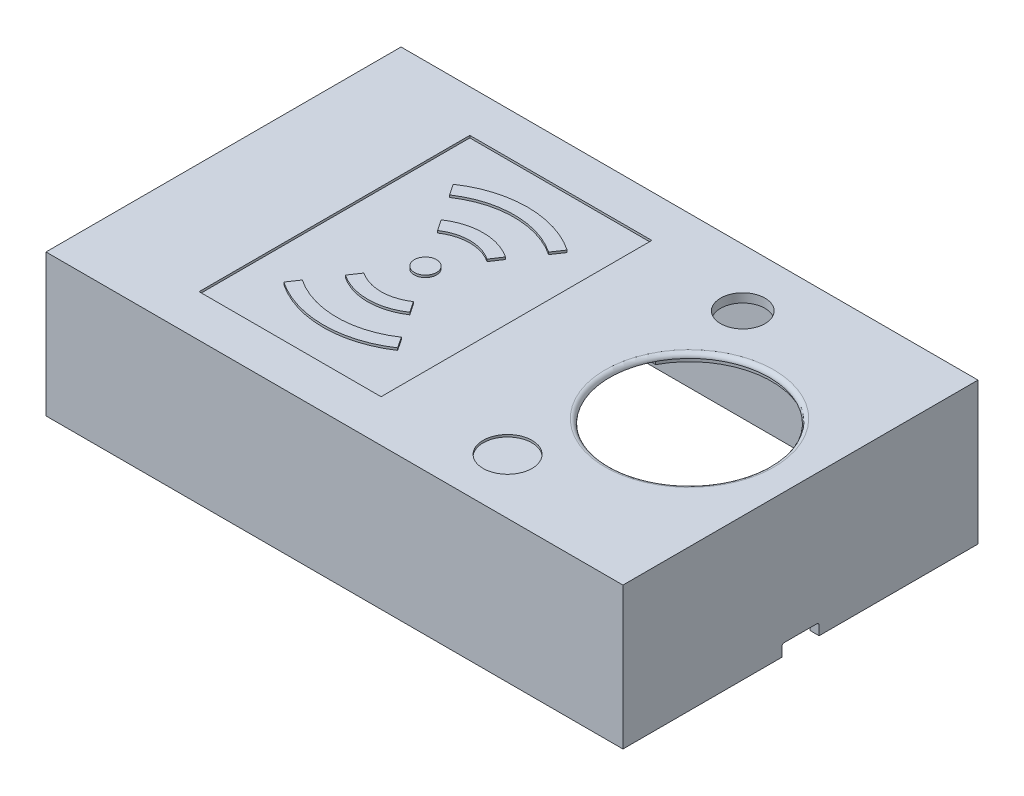
SolidWorks part; units mm, degrees
ref_plane "Plan de face" through (0, 0, 0) normal (0, 0, 1) x (1, 0, 0)
ref_plane "Plan de dessus" through (0, 0, 0) normal (0, 1, 0) x (1, 0, 0)
ref_plane "Plan de droite" through (0, 0, 0) normal (1, 0, 0) x (0, 0, -1)
sketch "Esquisse1" plane through (0, 0, 0) normal (0, 1, 0) x (1, 0, 0)
  line L1 (0, 0) -> (130, 0)
  line L2 (0, 0) -> (0, 80)
  line L3 (0, 80) -> (130, 80)
  line L4 (130, 0) -> (130, 80)
  dimension "D1" = 130
  dimension "D2" = 80
extrude "Boss.-Extru.1" add sketch "Esquisse1" along normal blind 2 contours L3 L4 L1 L2
sketch "Esquisse2" plane through (0, 0, 0) normal (0, -1, 0) x (1, 0, 0)
  line L1 (0, -80) -> (130, -80)
  line L2 (0, -80) -> (0, 0)
  line L3 (0, 0) -> (130, 0)
  line L4 (130, -80) -> (130, 0)
  line L5 (11.899, -78) -> (118.101, -78)
  line L6 (2, -68.101) -> (2, -11.899)
  line L7 (11.899, -2) -> (118.101, -2)
  line L8 (128, -68.101) -> (128, -11.899)
  circle A0 centre (123, -7) radius 5.1
  circle A1 centre (123, -73) radius 5.1
  circle A2 centre (7, -7) radius 5.1
  circle A3 centre (7, -73) radius 5.1
  arc A4 (2, -11.899) -> (11.899, -2) centre (7, -7) ccw
  arc A5 (118.101, -2) -> (128, -11.899) centre (123, -7) ccw
  arc A6 (11.899, -78) -> (2, -68.101) centre (7, -73) ccw
  arc A8 (128, -68.101) -> (118.101, -78) centre (123, -73) ccw
  dimension "D5" = 10.2
  dimension "D6" = 10.2
  dimension "D7" = 10.2
  dimension "D8" = 10.2
  dimension "D9" = 7
  dimension "D10" = 7
  dimension "D11" = 7
  dimension "D12" = 7
  dimension "D13" = 7
  dimension "D14" = 7
  dimension "D15" = 7
  dimension "D16" = 7
  dimension "D17" = 14
  dimension "D18" = 14
  dimension "D19" = 7
  dimension "D20" = 14
  dimension "D1" = 2
  dimension "D2" = 2
  dimension "D3" = 2
  dimension "D4" = 2
extrude "Boss.-Extru.2" add sketch "Esquisse2" along normal blind 30
sketch "Esquisse8" plane through (0, 0, 0) normal (0, -1, 0) x (1, 0, 0)
  circle A0 centre (123, -7) radius 5.5
  circle A1 centre (7, -7) radius 5.5
  circle A2 centre (7, -73) radius 5.5
  circle A3 centre (123, -73) radius 5.5
extrude "Boss.-Extru.6" add sketch "Esquisse8" along normal blind 5
sketch "Esquisse3" plane through (0, 0, 0) normal (0, -1, 0) x (1, 0, 0)
  line L0 (0, -40) -> (130, -40) construction
  line L1 (0, 0) -> (0, -80) construction
  line L2 (130, -80) -> (130, 0) construction
  circle A0 centre (105, -40) radius 18
  circle A1 centre (90, -67) radius 5
  dimension "D1" = 36
  dimension "D2" = 25
  dimension "D3" = 10
  dimension "D4" = 40
  dimension "D5" = 27
extrude "Enlèv. mat.-Extru.1" cut sketch "Esquisse3" against normal through all both and the other way through all
fillet "Congé1" radius 1 1 edges at (105, 2, -58)
sketch "Esquisse5" plane through (0, 2, 0) normal (0, 1, 0) x (1, 0, 0)
  line L0 (130, 0) -> (130, 80) construction
  line L1 (0, 0) -> (130, 0) construction
  line L2 (0, 80) -> (130, 80) construction
  line L3 (25, 9.5) -> (66, 9.5)
  line L4 (25, 9.5) -> (25, 70.5)
  line L5 (25, 70.5) -> (66, 70.5)
  line L6 (66, 9.5) -> (66, 70.5)
  line L7 (0, 0) -> (0, 80) construction
  circle A0 centre (91.5, 12.5) radius 5.5
  dimension "D1" = 11
  dimension "D2" = 38.5
  dimension "D3" = 12.5
  dimension "D4" = 41
  dimension "D5" = 61
  dimension "D6" = 9.5
  dimension "D7" = 25
extrude "Enlèv. mat.-Extru.2" cut sketch "Esquisse5" against normal blind 0.5
sketch "Esquisse7" plane through (0, 1.5, 0) normal (0, 1, 0) x (1, 0, 0)
  line L0 (25, 9.5) -> (66, 9.5) construction
  line L1 (25, 70.5) -> (25, 9.5) construction
  line L2 (32.6698, 59.0889) -> (34.3433, 56.599)
  line L3 (58.3302, 59.0889) -> (56.6567, 56.599)
  line L4 (38.2481, 50.7894) -> (39.9216, 48.2995)
  line L7 (52.7519, 50.7894) -> (51.0784, 48.2995)
  line L8 (51.0784, 31.7005) -> (52.7519, 29.2106)
  line L9 (39.9216, 31.7005) -> (38.2481, 29.2106)
  line L10 (34.3433, 23.401) -> (32.6698, 20.9111)
  line L11 (56.6567, 23.401) -> (58.3302, 20.9111)
  circle A0 centre (45.5, 40) radius 2.5
  arc A1 (51.0784, 48.2995) -> (39.9216, 48.2995) centre (45.5, 40) ccw
  arc A2 (52.7519, 50.7894) -> (38.2481, 50.7894) centre (45.5, 40) ccw
  arc A3 (56.6567, 56.599) -> (34.3433, 56.599) centre (45.5, 40) ccw
  arc A4 (58.3302, 59.0889) -> (32.6698, 59.0889) centre (45.5, 40) ccw
  arc A5 (32.6698, 20.9111) -> (58.3302, 20.9111) centre (45.5, 40) ccw
  arc A6 (34.3433, 23.401) -> (56.6567, 23.401) centre (45.5, 40) ccw
  arc A7 (39.9216, 31.7005) -> (51.0784, 31.7005) centre (45.5, 40) ccw
  arc A8 (38.2481, 29.2106) -> (52.7519, 29.2106) centre (45.5, 40) ccw
  dimension "D2" = 5
  dimension "D3" = 3
  dimension "D4" = 3
  dimension "D6" = 20
  dimension "D7" = 40
  dimension "D1" = 30.5
  dimension "D5" = 20.5
extrude "Boss.-Extru.5" add sketch "Esquisse7" along normal blind 0.5
sketch "Esquisse9" plane through (0, 0, 0) normal (0, -1, 0) x (1, 0, 0)
  line L0 (0, -40) -> (130, -40) construction
  line L1 (0, 0) -> (0, -80) construction
  line L2 (130, -80) -> (130, 0) construction
  line L3 (78.6, -31.3) -> (88.6733, -31.3)
  line L4 (78.6, -31.3) -> (78.6, -48.7)
  line L5 (78.6, -48.7) -> (88.6733, -48.7)
  line L6 (0, -80) -> (130, -80) construction
  arc A0 (88.6733, -48.7) -> (88.6733, -31.3) centre (105, -40) ccw
  dimension "D2" = 37
  dimension "D5" = 26.4
  dimension "D1" = 25
  dimension "D3" = 17.4
  dimension "D4" = 31.3
extrude "Enlèv. mat.-Extru.3" cut sketch "Esquisse9" against normal blind 1 contours L3 A0 L5 L4
ref_plane "Plan1" through (88.5, 0, 0) normal (-1, 0, 0) x (0, 0, 1)
sketch "Esquisse18" plane through (88.5, 0, 0) normal (-1, 0, 0) x (0, 0, 1)
  line L0 (-12.5, 7.4015) -> (-12.5, -18.6172) construction
  line L1 (-7.75, 0) -> (-4.75, 0)
  line L2 (0, 2) -> (0, -30) construction
  line L3 (-7.75, 0) -> (-7.75, -3)
  line L4 (-7.75, -3) -> (-6.75, -3)
  line L5 (-6.75, -3) -> (-6.75, -5)
  line L6 (-6.75, -5) -> (-7.5, -5)
  line L7 (-7.5, -5) -> (-6.75, -6.5)
  line L8 (-6.75, -6.5) -> (-5.75, -6.5)
  line L11 (-5.75, -6.5) -> (-4.75, 0)
  line L12 (0, 2) -> (-80, 2) construction
  line L13 (-17.25, 0) -> (-17.25, -3)
  line L14 (-17.25, -3) -> (-18.25, -3)
  line L15 (-18.25, -3) -> (-18.25, -5)
  line L16 (-18.25, -5) -> (-17.5, -5)
  line L17 (-17.5, -5) -> (-18.25, -6.5)
  line L18 (-18.25, -6.5) -> (-19.25, -6.5)
  line L19 (-19.25, -6.5) -> (-20.25, 0)
  line L20 (-17.25, 0) -> (-20.25, 0)
  point P14 (-7.8894, -6.5)
  point P15 (-6.75, -6.5)
  point P16 (0, 0)
  point P17 (-23.1553, -4.7784)
  dimension "D1" = 12.5
  dimension "D3" = 1.5
  dimension "D4" = 3
  dimension "D5" = 2
  dimension "D6" = 3
  dimension "D7" = 1
  dimension "D8" = 0.75
  dimension "D9" = 1
  dimension "D10" = 4.75
extrude "Boss.-Extru.8" add sketch "Esquisse18" along normal blind 3
fillet "Congé2" radius 0.8 8 edges at (85.5, 0, -6.25) (87, 0, -4.75) (87, 0, -7.75) (88.5, 0, -6.25) (88.5, 0, -18.75) (87, 0, -20.25) (87, 0, -17.25) (85.5, 0, -18.75)
ref_plane "Plan2" through (29.5, 0, 0) normal (1, 0, 0) x (0, 0, -1)
sketch "Esquisse19" plane through (29.5, 0, 0) normal (1, 0, 0) x (0, 0, -1)
  line L0 (55, 0) -> (55, -18.7859) construction
  line L1 (80, 2) -> (80, -30) construction
  line L2 (55, 0) -> (56.85, 0)
  line L3 (56.85, 0) -> (56.85, -5)
  line L4 (56.85, -5) -> (57, -5)
  line L5 (57, -5) -> (56.1, -7.9)
  line L6 (56.1, -7.9) -> (55, -7.9)
  line L7 (55, -7.9) -> (55, 0)
  line L8 (0, 2) -> (80, 2) construction
  dimension "D1" = 25
  dimension "D2" = 1.85
  dimension "D3" = 2
  dimension "D4" = 1.1
  dimension "D5" = 5
  dimension "D6" = 2.9
  dimension "D7" = 2
ref_plane "Plan3" through (59.5, 0, 0) normal (1, 0, 0) x (0, 0, -1)
sketch "Esquisse20" plane through (59.5, 0, 0) normal (1, 0, 0) x (0, 0, -1)
  line L0 (18.5, 0) -> (18.5, -17.3873) construction
  line L1 (0, 2) -> (80, 2) construction
  line L2 (55, 0) -> (55, -18.7859) construction
  line L3 (18.5, 0) -> (20.35, 0)
  line L4 (20.35, 0) -> (20.35, -5)
  line L5 (20.35, -5) -> (20.5, -5)
  line L6 (20.5, -5) -> (19.6, -7.9)
  line L7 (19.6, -7.9) -> (18.5, -7.9)
  line L8 (18.5, -7.9) -> (18.5, 0)
  point P8 (24.396, -6.0728)
  point P10 (24.396, -6.6302)
  dimension "D1" = 36.5
  dimension "D2" = 5
  dimension "D3" = 2.9
  dimension "D4" = 1.85
  dimension "D5" = 2
  dimension "D6" = 1.1
  dimension "D7" = 2
revolve "Révolution1" add sketch "Esquisse19" angle 360 about L0
revolve "Révolution2" add sketch "Esquisse20" angle 360 about L0
fillet "Congé3" radius 0.8 2 edges at (29.5, 0, -53.15) (59.5, 0, -16.65)
sketch "Esquisse21" plane through (29.5, 0, 0) normal (1, 0, 0) x (0, 0, -1)
  line L0 (54.625, -10.5) -> (54.625, -0.5)
  line L2 (55.375, -0.5) -> (55.375, -10.5)
  line L3 (55.375, -10.5) -> (54.625, -10.5)
  line L4 (80, 2) -> (80, -30) construction
  line L5 (0, 2) -> (80, 2) construction
  line L6 (54.625, -0.5) -> (55.375, -0.5) construction
  arc A0 (55.375, -0.5) -> (54.625, -0.5) centre (55, -0.5) ccw
  dimension "D2" = 0.375
  dimension "D1" = 10
  dimension "D3" = 24.625
  dimension "D4" = 2.5
  dimension "D5" = 0.75
extrude "Enlèv. mat.-Extru.4" cut sketch "Esquisse21" against normal blind 3
extrude "Enlèv. mat.-Extru.5" cut sketch "Esquisse21<2>" along normal blind 17
sketch "Esquisse21<2>" plane through (29.5, 0, 0) normal (1, 0, 0) x (0, 0, -1) same geometry as "Esquisse21"
sketch "Esquisse22" plane through (59.5, 0, 0) normal (1, 0, 0) x (0, 0, -1)
  line L0 (18.125, -0.5) -> (18.125, -10.5)
  line L1 (18.125, -10.5) -> (18.875, -10.5)
  line L2 (18.875, -10.5) -> (18.875, -0.5)
  line L3 (18.125, -0.5) -> (18.875, -0.5) construction
  line L4 (0, 2) -> (80, 2) construction
  line L5 (54.625, -0.8) -> (54.625, -5) construction
  arc A0 (18.875, -0.5) -> (18.125, -0.5) centre (18.5, -0.5) ccw
  dimension "D3" = 2.5
  dimension "D1" = 10
  dimension "D2" = 0.75
  dimension "D4" = 35.75
extrude "Enlèv. mat.-Extru.6" cut sketch "Esquisse22" against normal blind 17
extrude "Enlèv. mat.-Extru.7" cut sketch "Esquisse22<2>" along normal blind 11
sketch "Esquisse22<2>" plane through (59.5, 0, 0) normal (1, 0, 0) x (0, 0, -1) same geometry as "Esquisse22"
sketch "Esquisse23" plane through (130, 0, 0) normal (1, 0, 0) x (0, 0, -1)
  line L0 (40, -30) -> (40, -21.1867) construction
  line L1 (80, -30) -> (0, -30) construction
  line L3 (35.8, -30) -> (44.2, -30)
  line L4 (35.8, -30) -> (35.8, -27.4)
  line L5 (35.8, -27.4) -> (44.2, -27.4)
  line L6 (44.2, -30) -> (44.2, -27.4)
  dimension "D1" = 8.4
  dimension "D2" = 4.2
  dimension "D3" = 2.6
extrude "Enlèv. mat.-Extru.8" cut sketch "Esquisse23" against normal blind 11
fillet "Congé4" radius 0.5 2 edges at (129, -27.4, -35.8) (129, -27.4, -44.2)
